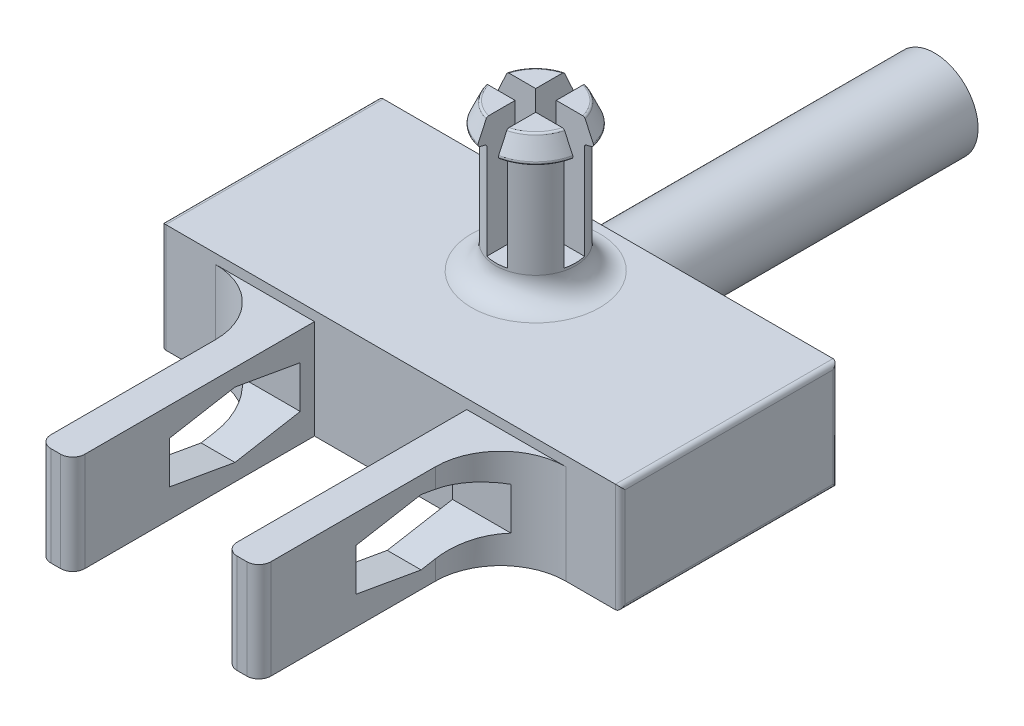
SolidWorks part; units mm, degrees
ref_plane "Front Plane" through (0, 0, 0) normal (0, 0, 1) x (1, 0, 0)
ref_plane "Top Plane" through (0, 0, 0) normal (0, 1, 0) x (1, 0, 0)
ref_plane "Right Plane" through (0, 0, 0) normal (1, 0, 0) x (0, 0, -1)
sketch "Szkic1" plane through (0, 0, 0) normal (0, 1, 0) x (1, 0, 0)
  line L0 (0, -13.1707) -> (0, 4.5) construction
  line L1 (4.55, -4.5) -> (-4.55, -4.5)
  line L2 (9.5, -4.5) -> (9.5, 4.5)
  line L3 (9.5, 4.5) -> (-9.5, 4.5)
  line L4 (-9.5, -4.5) -> (-9.5, 4.5)
  line L5 (9.5, -4.5) -> (-9.5, 4.5) construction
  line L6 (9.5, 4.5) -> (-9.5, -4.5) construction
  line L7 (-9.5, -4.5) -> (-4.55, -4.5)
  line L10 (2.5793, 4.5) -> (-2.5793, 4.5)
  line L13 (-4.55, -4.5) -> (-7.25, -4.5)
  line L14 (-4.55, -4.5) -> (-3.15, -4.5)
  line L15 (-4.55, -4.5) -> (-4.55, -14.5)
  line L16 (-4.55, -14.5) -> (-3.15, -14.5)
  line L17 (-3.15, -4.5) -> (-3.15, -14.5)
  line L18 (4.55, -4.5) -> (3.15, -4.5)
  line L19 (4.55, -4.5) -> (4.55, -14.5)
  line L20 (4.55, -14.5) -> (3.15, -14.5)
  line L21 (3.15, -4.5) -> (3.15, -14.5)
  line L22 (4.55, -4.5) -> (9.5, -4.5)
  line L23 (-4.55, -4.5) -> (-4.55, -7.2)
  line L26 (4.55, -4.5) -> (7.25, -4.5)
  line L27 (4.55, -4.5) -> (4.55, -7.2)
  arc A0 (-4.55, -7.2) -> (-7.25, -4.5) centre (-7.25, -7.2) ccw
  arc A1 (7.25, -4.5) -> (4.55, -7.2) centre (7.25, -7.2) ccw
  point P0 (0, 0)
  dimension "D1" = 9
  dimension "D2" = 19
  dimension "D3" = 10
  dimension "D4" = 1.4
  dimension "D5" = 6.3
  dimension "D6" = 2.7
extrude "Dodanie-wyciągnięcie1" add sketch "Szkic1" along normal blind 4.5 contours L1 L22 L2 L3 L4 L7 region at (0, 0, 0)
extrude "Dodanie-wyciągnięcie2" add sketch "Szkic1<7>" along normal blind 4.1 contours A0 L15 L7 | L17 L1 L15 L16 | A1 L22 L19 | L1 L21 L20 L19 region at (3.85, 0, 9.5) region at (5.1531, 0, 5.1031) region at (-3.85, 0, 9.5) region at (-5.1531, 0, 5.1031)
sketch "Szkic1<7>" plane through (0, 0, 0) normal (0, 1, 0) x (1, 0, 0) same geometry as "Szkic1"
ref_plane "Płaszczyzna1" through (0, 0, -4.5) normal (0, 0, -1) x (-1, 0, 0)
sketch "Szkic2" plane through (0, 0, -4.5) normal (0, 0, -1) x (-1, 0, 0)
  line L0 (0, 0) -> (0, 4.5) construction
  line L1 (-9.5, 4.5) -> (9.5, 4.5) construction
  circle A0 centre (0, 2.25) radius 1.8
  point P5 (0, 2.25)
  dimension "D1" = 3.6
extrude "Dodanie-wyciągnięcie3" add sketch "Szkic2" along normal blind 13.5
ref_plane "Płaszczyzna2" through (-3.15, 0, 0) normal (1, 0, 0) x (0, 0, -1)
sketch "Szkic3" plane through (-3.15, 0, 0) normal (1, 0, 0) x (0, 0, -1)
  line L0 (-7.79, 3.4) -> (-10.49, 2.9239)
  line L1 (-10.49, 2.9239) -> (-10.49, 1.1761)
  line L2 (-10.49, 1.1761) -> (-7.79, 0.7)
  line L3 (-7.79, 0.7) -> (-5.09, 1.1761)
  line L4 (-5.09, 1.1761) -> (-5.09, 2.9239)
  line L5 (-5.09, 2.9239) -> (-7.79, 3.4)
  line L7 (-4.5, 4.1) -> (-14.5, 4.1) construction
  line L8 (-4.5, 0) -> (-14.5, 0) construction
  dimension "D1" = 0.7
  dimension "D2" = 0.7
  dimension "D3" = 100
  dimension "D4" = 100
  dimension "D5" = 5.4
extrude "Wytnij-wyciągnięcie2" cut sketch "Szkic3" along normal through all both and the other way through all
fillet "Zaokrąglenie1" radius 0.5 4 edges at (3.15, 2.05, 14.5) (4.55, 2.05, 14.5) (-4.55, 2.05, 14.5) (-3.15, 2.05, 14.5)
fillet "Zaokrąglenie2" radius 0.2 8 edges at (-9.5, 2.25, -4.5) (-9.5, 4.5, 0) (9.5, 0, 0) (-9.5, 2.25, 4.5) (9.5, 2.25, 4.5) (9.5, 2.25, -4.5) (9.5, 4.5, 0) (-9.5, 0, 0)
ref_plane "Płaszczyzna3" through (0, 4.5, 0) normal (0, 1, 0) x (1, 0, 0)
sketch "Szkic4" plane through (0, 4.5, 0) normal (0, 1, 0) x (1, 0, 0)
  line L0 (-9.3, 1.5) -> (9.3, 1.5) construction
  line L1 (2.475, 4.5) -> (-2.475, 4.5) construction
  line L3 (-9.3, 4.5) -> (-9.3, -4.5) construction
  line L4 (9.3, -4.5) -> (9.3, 4.5) construction
  circle A0 centre (0, 1.5) radius 1.65
  point P6 (0, 1.5)
  dimension "D1" = 3.3
  dimension "D2" = 3
extrude "Dodanie-wyciągnięcie4" add sketch "Szkic4" along normal blind 5.1
ref_plane "Płaszczyzna4" through (0, 9.6, 0) normal (0, 1, 0) x (1, 0, 0)
sketch "Szkic5" plane through (0, 9.6, 0) normal (0, 1, 0) x (1, 0, 0)
  line L0 (0, 3.15) -> (0, -0.15) construction
  circle A0 centre (0, 1.5) radius 1.65 construction
  circle A1 centre (0, 1.5) radius 1.65
  point P5 (0, 1.5)
  dimension "D1" = 3.3
extrude "Dodanie-wyciągnięcie5" add sketch "Szkic5" along normal blind 1
fillet "Zaokrąglenie4" radius 1 1 edges at (0, 4.5, 0.15)
ref_axis "Oś1" through (0, 16.6, -1.5) along (0, -1, 0)
ref_point "Punkt1"
ref_point "Punkt2"
ref_plane "Płaszczyzna5" through (0, 0, 0) normal (1, 0, 0) x (0, 0, -1)
ref_plane "Płaszczyzna Dolnia" through (0, 0, 0) normal (0, -1, 0) x (-1, 0, 0)
ref_plane "Płaszczyzna6" through (0, 10.5, 0) normal (0, 1, 0) x (1, 0, 0)
sketch "Szkic7" plane through (0, 0, 0) normal (1, 0, 0) x (0, 0, -1)
  line L6 (3.15, 10.6) -> (3.15, 9.6)
  line L8 (3.15, 5.5) -> (3.15, 10.6) construction
  line L9 (3.15, 9.6) -> (3.55, 9.7072)
  line L10 (3.55, 9.7072) -> (3.15, 10.6)
  line L13 (1.5, 16.6) -> (1.5, 5.5) construction
  line L14 (3.15, 5.5) -> (3.15, 10.6) construction
  line L15 (3.15, 5.5) -> (3.15, 10.6) construction
  line L16 (4.95, 4.5) -> (-4.95, 4.5) construction
  point P8 (3.15, 9.6358)
  point P11 (3.55, 10.4267)
  point P12 (3.3783, 10.6)
  point P13 (3.15, 10.198)
  point P16 (3.55, 10.2867)
  point P19 (3.15, 10.5884)
  dimension "D1" = 2.05
  dimension "D2" = 75
  dimension "D4" = 5.1
revolve "Obrót1" add sketch "Szkic7" angle 360 about axis through (0, 16.6, -1.5) along (0, -1, 0)
fillet "Zaokrąglenie5" radius 0.1 3 edges at (0, 9.6, 0.15) (0, 9.7072, 0.55) (0, 10.6, 0.15)
ref_plane "Płaszczyzna7" through (0, 10.6, 0) normal (0, 1, 0) x (1, 0, 0)
sketch "Szkic6" plane through (0, 10.6, 0) normal (0, 1, 0) x (1, 0, 0)
  line L0 (0.425, 4.7145) -> (0.425, 1.925)
  line L1 (-0.425, 4.7145) -> (-0.425, 1.925)
  line L2 (3.2145, 1.925) -> (0.425, 1.925)
  line L3 (3.2145, 1.075) -> (0.425, 1.075)
  line L4 (-0.425, 1.075) -> (-3.2145, 1.075)
  line L5 (-0.425, 1.925) -> (-3.2145, 1.925)
  line L6 (0.425, 1.075) -> (0.425, -1.7145)
  line L7 (-0.425, 1.075) -> (-0.425, -1.7145)
  line L8 (-0.425, 1.925) -> (0.425, 1.075) construction
  arc A4 (0.425, 4.7145) -> (-0.425, 4.7145) centre (0, 1.5) ccw
  arc A5 (3.2145, 1.075) -> (3.2145, 1.925) centre (0, 1.5) ccw
  arc A6 (-0.425, -1.7145) -> (0.425, -1.7145) centre (0, 1.5) ccw
  arc A7 (-3.2145, 1.925) -> (-3.2145, 1.075) centre (0, 1.5) ccw
  point P18 (0, 1.5)
  dimension "D1" = 0.85
  dimension "D2" = 0.85
extrude "Wytnij-wyciągnięcie3" cut sketch "Szkic6" against normal blind 5
